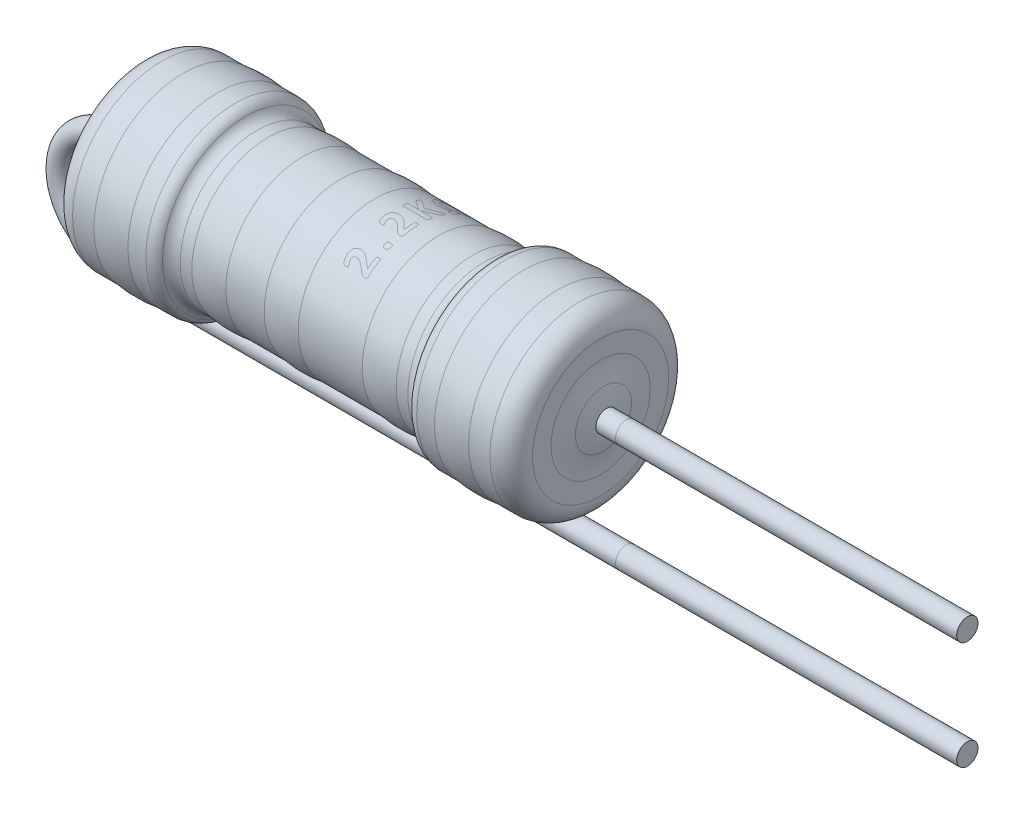
SolidWorks part; units mm, degrees
ref_plane "Front Plane" through (0, 0, 0) normal (0, 0, 1) x (1, 0, 0)
ref_plane "Top Plane" through (0, 0, 0) normal (0, 1, 0) x (1, 0, 0)
ref_plane "Right Plane" through (0, 0, 0) normal (1, 0, 0) x (0, 0, -1)
sketch "Sketch Set Wire Width" plane through (0, 0, 0) normal (0, 0, 1) x (1, 0, 0)
  line L0 (0, 0) -> (6, 0)
  line L1 (6, -2.54) -> (-6, -2.54)
  line L2 (6, 0) -> (14.0102, 0)
  line L3 (-6, 0) -> (-6, -2.54) construction
  line L4 (-6, 0) -> (-6, -2.54) construction
  line L5 (6, -2.54) -> (6, 0) construction
  line L6 (6, -2.54) -> (14.0102, -2.54)
  line L7 (14.0102, -2.54) -> (14.0102, 0) construction
  line L8 (-6, 0) -> (0, 0)
  arc A0 (-6, 0) -> (-6, -2.54) centre (-6, -1.27) ccw
  dimension "D2" = 2.54
  dimension "D3" = 30
  dimension "D1" = 12
  dimension "D4" = 6
sketch "Sketch Wire Diameter" plane through (0, 0, 0) normal (1, 0, 0) x (0, 0, -1)
  circle A0 centre (0, 0) radius 0.25
  dimension "D1" = 0.5
sweep "SET WIRE LENGTH" add profiles "Sketch Wire Diameter" path "Sketch Set Wire Width"
sketch "Sketch3" plane through (0, 0, 0) normal (0, 0, 1) x (1, 0, 0)
  line L0 (-5.4, 0) -> (5.4, 0)
  line L1 (0, 0) -> (0, 1.8) construction
  line L2 (-2.9, 1.8) -> (2.9, 1.8)
  line L3 (-5.4, 0) -> (-5.4, 1.6)
  line L4 (-4.9, 2.1) -> (-3.18, 2.1)
  line L5 (-2.9, 1.82) -> (-2.9, 1.8)
  line L6 (5.4, 0) -> (5.4, 1.6)
  line L7 (4.9, 2.1) -> (3.18, 2.1)
  line L8 (2.9, 1.82) -> (2.9, 1.8)
  arc A0 (-5.4, 1.6) -> (-4.9, 2.1) centre (-4.9, 1.6) cw
  arc A1 (5.4, 1.6) -> (4.9, 2.1) centre (4.9, 1.6) ccw
  arc A2 (-3.18, 2.1) -> (-2.9, 1.82) centre (-3.18, 1.82) cw
  arc A3 (3.18, 2.1) -> (2.9, 1.82) centre (3.18, 1.82) ccw
  dimension "D5" = 0.5
  dimension "D6" = 0.28
  dimension "D1" = 10.8
  dimension "D2" = 5.8
  dimension "D3" = 1.8
  dimension "D4" = 2.1
revolve "Revolve2" add sketch "Sketch3" angle 360 about L0
fillet "Fillet1" radius 0.3 2 edges at (2.9, 0, 1.8) (-2.9, 0, 1.8)
sketch "Sketch5" plane through (0, 0, 0) normal (0, 0, 1) x (1, 0, 0)
  line L0 (0, 0) -> (2, 0) construction
  line L1 (0, 0) -> (-0.3, 0) construction
  line L2 (-0.3, 0) -> (-2, 0) construction
  line L3 (-2, 0) -> (-4, 0) construction
  line L4 (2, 0) -> (4, 0) construction
  line L5 (-4, 0) -> (-4, 2.1) construction
  line L6 (-0.3, 0) -> (-0.3, 1.8) construction
  line L7 (-2, 0) -> (-2, 1.8) construction
  line L8 (2, 0) -> (2, 1.8) construction
  line L9 (4, 0) -> (4, 2.1) construction
  line L10 (-4, 2.1) -> (-4, 2.13) construction
  line L11 (-4.9, 2.1) -> (-3.18, 2.1) construction
  line L12 (4.9, 2.1) -> (3.18, 2.1) construction
  line L13 (-2.9, 1.8) -> (2.9, 1.8) construction
  line L14 (-2, 1.8) -> (-2, 1.83) construction
  line L17 (-4.4, 2.1) -> (-3.6, 2.1)
  line L19 (-5.4, 0) -> (5.4, 0) construction
  line L22 (-2.4, 1.8) -> (-1.6, 1.8) construction
  line L26 (-0.7, 1.8) -> (0.1, 1.8) construction
  line L30 (1.6, 1.8) -> (2.4, 1.8) construction
  line L34 (3.6, 2.1) -> (4.4, 2.1) construction
  line L36 (-0.3, 1.8) -> (-0.3, 1.83) construction
  line L37 (2, 1.8) -> (2, 1.83) construction
  line L38 (4, 2.1) -> (4, 2.13) construction
  arc A0 (-4.4, 2.1) -> (-3.6, 2.1) centre (-4, -0.5517) cw
  arc A1 (-2.4, 1.8) -> (-1.6, 1.8) centre (-2, -0.8517) cw construction
  arc A2 (-0.7, 1.8) -> (0.1, 1.8) centre (-0.3, -0.8517) cw construction
  arc A3 (1.6, 1.8) -> (2.4, 1.8) centre (2, -0.8517) cw construction
  arc A4 (3.6, 2.1) -> (4.4, 2.1) centre (4, -0.5517) cw construction
  dimension "D3" = 0.8
  dimension "D1" = 4
  dimension "D2" = 4
  dimension "D4" = 0.03
  dimension "D5" = 2
  dimension "D6" = 2
  dimension "D7" = 1.7
revolve "Band 1" add sketch "Sketch5" angle 360 about L2
sketch "Sketch8" plane through (0, 0, 0) normal (0, 0, 1) x (1, 0, 0)
  line L0 (-2.4, 1.8) -> (-1.6, 1.8) construction
  line L1 (-2.4, 1.8) -> (-1.6, 1.8)
  arc A0 (-1.6, 1.8) -> (-2.4, 1.8) centre (-2, -0.8517) ccw construction
  arc A1 (-1.6, 1.8) -> (-2.4, 1.8) centre (-2, -0.8517) ccw
revolve "Band 2" add sketch "Sketch8" angle 360 about L2
sketch "Sketch9" plane through (0, 0, 0) normal (0, 0, 1) x (1, 0, 0)
  line L0 (-0.7, 1.8) -> (0.1, 1.8) construction
  line L1 (-0.7, 1.8) -> (0.1, 1.8)
  arc A0 (0.1, 1.8) -> (-0.7, 1.8) centre (-0.3, -0.8517) ccw construction
  arc A1 (0.1, 1.8) -> (-0.7, 1.8) centre (-0.3, -0.8517) ccw
revolve "Band 3" add sketch "Sketch9" angle 360 about L2
sketch "Sketch10" plane through (0, 0, 0) normal (0, 0, 1) x (1, 0, 0)
  line L0 (1.6, 1.8) -> (2.4, 1.8) construction
  line L1 (1.6, 1.8) -> (2.4, 1.8)
  arc A0 (2.4, 1.8) -> (1.6, 1.8) centre (2, -0.8517) ccw construction
  arc A1 (2.4, 1.8) -> (1.6, 1.8) centre (2, -0.8517) ccw
revolve "Band 4" add sketch "Sketch10" angle 360 about L0
sketch "Sketch11" plane through (0, 0, 0) normal (0, 0, 1) x (1, 0, 0)
  line L0 (3.6, 2.1) -> (4.4, 2.1) construction
  line L1 (3.6, 2.1) -> (4.4, 2.1)
  arc A0 (4.4, 2.1) -> (3.6, 2.1) centre (4, -0.5517) ccw construction
  arc A1 (4.4, 2.1) -> (3.6, 2.1) centre (4, -0.5517) ccw
revolve "Band 5" add sketch "Sketch11" angle 360 about L4
sketch "Sketch12" plane through (0, 0, 0) normal (0, 0, 1) x (1, 0, 0)
  line L0 (-5.35, 0) -> (5.35, 0) construction
  line L1 (-5.35, 1) -> (-5.35, 0)
  line L2 (5.35, 1) -> (5.35, 0)
  line L3 (-5.35, 0) -> (-5.55, 0)
  line L4 (5.35, 0) -> (5.55, 0)
  arc A0 (-5.35, 1) -> (-5.55, 0) centre (-2.95, 0) ccw
  arc A1 (5.35, 1) -> (5.55, 0) centre (2.95, 0) cw
  dimension "D3" = 0.2
  dimension "D4" = 2.6
  dimension "D1" = 10.7
  dimension "D2" = 1
revolve "Revolve10" add sketch "Sketch12" angle 360 about L0
fillet "Fillet2" radius 2 2 edges at (5.4, 0, 0.8703) (-5.4, 0, -0.8703)
ref_plane "Plane2" through (0, 3, 0) normal (0, 1, 0) x (1, 0, 0)
sketch "Sketch13" plane through (0, 3, 0) normal (0, 1, 0) x (1, 0, 0)
  line L0 (0, 0) -> (1.15, 0) construction
  line L1 (1.15, 1.75) -> (1.15, -1.75) construction
  text T0 "2.2KΩ" font "Calibri" height 0.6
  dimension "D1" = 3.5
  dimension "D2" = 1.15
wrap "Wrap1" sketch "Sketch13" wrap type scribe source sketch "Sketch13" face at (0.1, 1.8, 0)
